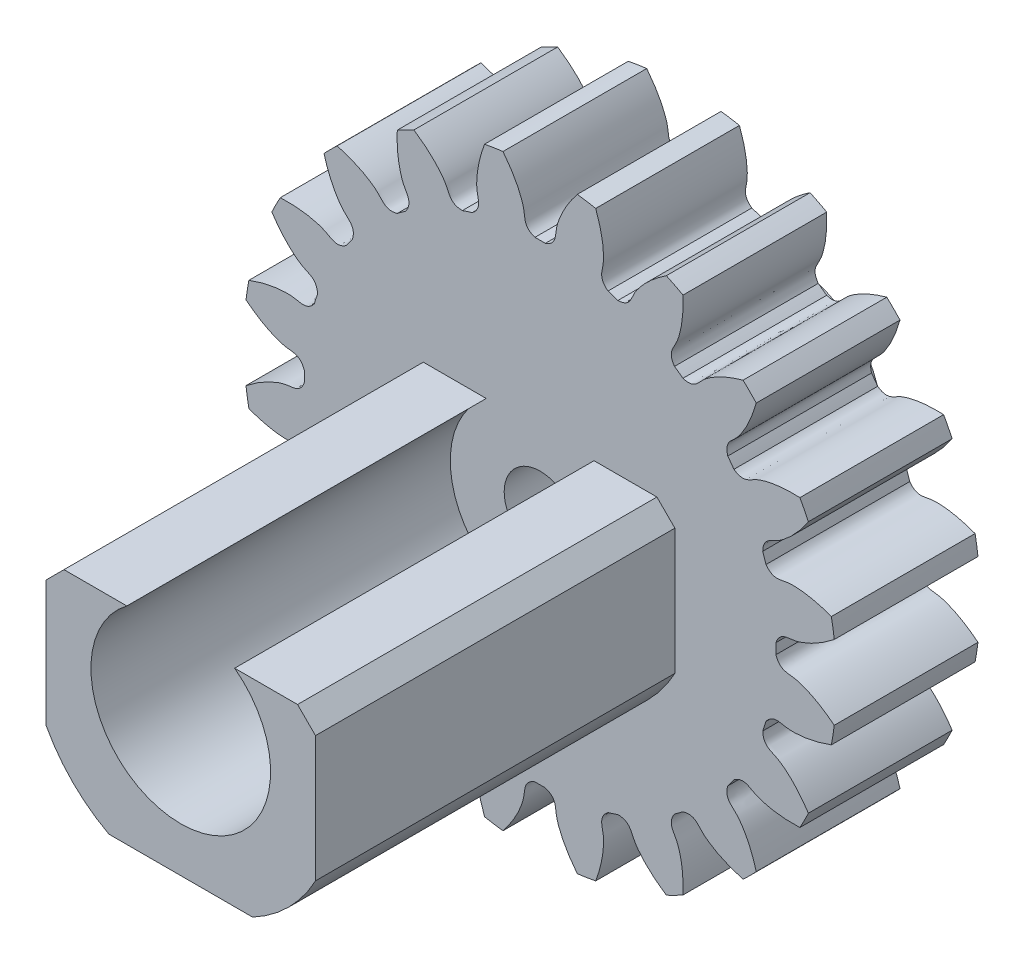
SolidWorks part; units mm, degrees
material "1060 合金"
ref_plane "前视基准面" through (0, 0, 0) normal (0, 0, 1) x (1, 0, 0)
ref_plane "上视基准面" through (0, 0, 0) normal (0, 1, 0) x (1, 0, 0)
ref_plane "右视基准面" through (0, 0, 0) normal (1, 0, 0) x (0, 0, -1)
sketch "草图1" plane through (0, 0, 0) normal (0, 0, 1) x (1, 0, 0)
  circle A0 centre (0, 0) radius 16.5
extrude "凸台-拉伸1" add sketch "草图1" along normal blind 8
ref_axis "基准轴1" through (0, 0, 8) along (0, 0, -1)
sketch "草图2" plane through (0, 0, 0) normal (0, 0, 1) x (1, 0, 0)
  line L0 (0, 0) -> (0, 16.5) construction
  circle A0 centre (0, 0) radius 16.5 construction
  arc A1 (0.29, 13.1218) -> (-0.29, 13.1218) centre (0, 0) ccw
  arc A2 (4.7717, 18.7474) -> (-4.7717, 18.7474) centre (0, 0) ccw
  spline S0 degree 3 poles (0.29, 13.1218) (0.9168, 13.3402) (0.8356, 13.7807) (0.9193, 14.205) (0.9283, 14.2463) (0.9395, 14.293) (0.9529, 14.3448) (0.969, 14.4018) (0.9878, 14.4638) (1.0095, 14.5309) (1.0345, 14.6028) (1.0629, 14.6795) (1.0948, 14.7608) (1.1305, 14.8467) (1.1702, 14.9371) (1.2141, 15.0317) (1.2623, 15.1305) (1.315, 15.2334) (1.3725, 15.3401) (1.4349, 15.4506) (1.5023, 15.5646) (1.575, 15.6821) (1.653, 15.8029) (1.7366, 15.9267) (1.826, 16.0534) (1.9211, 16.1829) (2.0223, 16.3149) (2.1296, 16.4493) (2.2432, 16.5859) (2.3632, 16.7244) (2.4897, 16.8646) (2.6229, 17.0065) (2.7628, 17.1496) (2.9095, 17.2939) (3.0632, 17.4391) (3.224, 17.585) (3.3918, 17.7313) (3.567, 17.8779) (3.7493, 18.0245) (3.9391, 18.1709) (4.1363, 18.3167) (4.4122, 18.5125) (4.6259, 18.6545) (4.7717, 18.7474) knots 0 0 0 0 0.165916 0.170906 0.176664 0.183189 0.190482 0.198542 0.207371 0.216967 0.22733 0.238462 0.250361 0.263027 0.276462 0.290664 0.305634 0.321371 0.337876 0.355149 0.37319 0.391998 0.411574 0.431917 0.453028 0.474907 0.497554 0.520968 0.54515 0.570099 0.595817 0.622302 0.649554 0.677575 0.706363 0.735918 0.766242 0.797333 0.829191 0.861818 0.895212 0.929373 1 1 1 1
  spline S1 degree 3 poles (-0.29, 13.1218) (-0.9168, 13.3402) (-0.8356, 13.7807) (-0.9193, 14.205) (-0.9283, 14.2463) (-0.9395, 14.293) (-0.9529, 14.3448) (-0.969, 14.4018) (-0.9878, 14.4638) (-1.0095, 14.5309) (-1.0345, 14.6028) (-1.0629, 14.6795) (-1.0948, 14.7608) (-1.1305, 14.8467) (-1.1702, 14.9371) (-1.2141, 15.0317) (-1.2623, 15.1305) (-1.315, 15.2334) (-1.3725, 15.3401) (-1.4349, 15.4506) (-1.5023, 15.5646) (-1.575, 15.6821) (-1.653, 15.8029) (-1.7366, 15.9267) (-1.826, 16.0534) (-1.9211, 16.1829) (-2.0223, 16.3149) (-2.1296, 16.4493) (-2.2432, 16.5859) (-2.3632, 16.7244) (-2.4897, 16.8646) (-2.6229, 17.0065) (-2.7628, 17.1496) (-2.9095, 17.2939) (-3.0632, 17.4391) (-3.224, 17.585) (-3.3918, 17.7313) (-3.567, 17.8779) (-3.7493, 18.0245) (-3.9391, 18.1709) (-4.1363, 18.3167) (-4.4122, 18.5125) (-4.6259, 18.6545) (-4.7717, 18.7474) knots 0 0 0 0 0.165916 0.170906 0.176664 0.183189 0.190482 0.198542 0.207371 0.216967 0.22733 0.238462 0.250361 0.263027 0.276462 0.290664 0.305634 0.321371 0.337876 0.355149 0.37319 0.391998 0.411574 0.431917 0.453028 0.474907 0.497554 0.520968 0.54515 0.570099 0.595817 0.622302 0.649554 0.677575 0.706363 0.735918 0.766242 0.797333 0.829191 0.861818 0.895212 0.929373 1 1 1 1
extrude "切除-拉伸1" cut sketch "草图2" along normal through all
pattern_circular "阵列(圆周)1" count 20 every 18 about axis through (0, 0, 8) along (0, 0, -1) of "切除-拉伸1"
sketch "草图3" plane through (0, 0, 0) normal (0, 0, 1) x (1, 0, 0)
  circle A0 centre (0, 0) radius 15 construction
  dimension "Dn" = 30
sketch "草图4" plane through (0, 0, 0) normal (0, 0, -1) x (-1, 0, 0)
  circle A0 centre (0, 0) radius 6
  dimension "D1" = 12
extrude "凸台-拉伸2" add sketch "草图4" along normal blind 1
sketch "草图5" plane through (0, 0, -1) normal (0, 0, -1) x (-1, 0, 0)
  circle A0 centre (0, 0) radius 5
  dimension "D1" = 10
extrude "凸台-拉伸3" add sketch "草图5" along normal blind 5
sketch "草图6" plane through (0, 0, 8) normal (0, 0, 1) x (1, 0, 0)
  circle A0 centre (0, 0) radius 8.5
  dimension "D1" = 17
extrude "凸台-拉伸4" add sketch "草图6" along normal blind 20
sketch "草图7" plane through (0, 0, 28) normal (0, 0, 1) x (1, 0, 0)
  circle A0 centre (0, 0) radius 5
  dimension "D1" = 10
extrude "切除-拉伸2" cut sketch "草图7" against normal blind 20
sketch "草图8" plane through (0, 0, 28) normal (0, 0, 1) x (1, 0, 0)
  line L1 (-9.1035, 11.8786) -> (11.5778, 11.8786)
  line L2 (-9.1035, 11.8786) -> (-9.1035, 4)
  line L3 (-9.1035, 4) -> (11.5778, 4)
  line L4 (11.5778, 11.8786) -> (11.5778, 4)
  dimension "D1" = 4
extrude "切除-拉伸3" cut sketch "草图8" against normal blind 20
sketch "草图9" plane through (0, 0, 28) normal (0, 0, 1) x (1, 0, 0)
  line L2 (-7.5, 4) -> (-7.5, -4)
  line L3 (-4, -7.5) -> (4, -7.5)
  line L4 (7.5, 4) -> (7.5, -4)
  line L5 (-7.5, 7.5) -> (7.5, -7.5) construction
  line L6 (-7.5, -7.5) -> (7.5, 7.5) construction
  arc A0 (-4, -7.5) -> (4, -7.5) centre (0, 0) ccw
  arc A1 (7.5, -4) -> (7.5, 4) centre (0, 0) ccw
  arc A2 (-7.5, 4) -> (-7.5, -4) centre (0, 0) ccw
  point P0 (0, 0)
  dimension "D1" = 15
extrude "切除-拉伸4" cut sketch "草图9" against normal blind 20
chamfer "倒角1" distance 1 angle 45 2 edges at (-7.5, 4, 18) (7.5, 4, 18)
sketch "草图10" plane through (0, -7.5, 0) normal (0, -1, 0) x (1, 0, 0)
  line L0 (4, 28) -> (-4, 28) construction
  line L2 (4, 8) -> (4, 28) construction
  circle A0 centre (0, 18) radius 1.5
  dimension "D1" = 3
  dimension "D2" = 10
  dimension "D3" = 4
extrude "切除-拉伸5" cut sketch "草图10" against normal blind 10
sketch "草图11" plane through (0, 0, -6) normal (0, 0, -1) x (-1, 0, 0)
  circle A0 centre (0, 0) radius 2
  dimension "D1" = 4
extrude "切除-拉伸6" cut sketch "草图11" against normal up to surface (14 mm away) up to face at (0, 0, 8)
